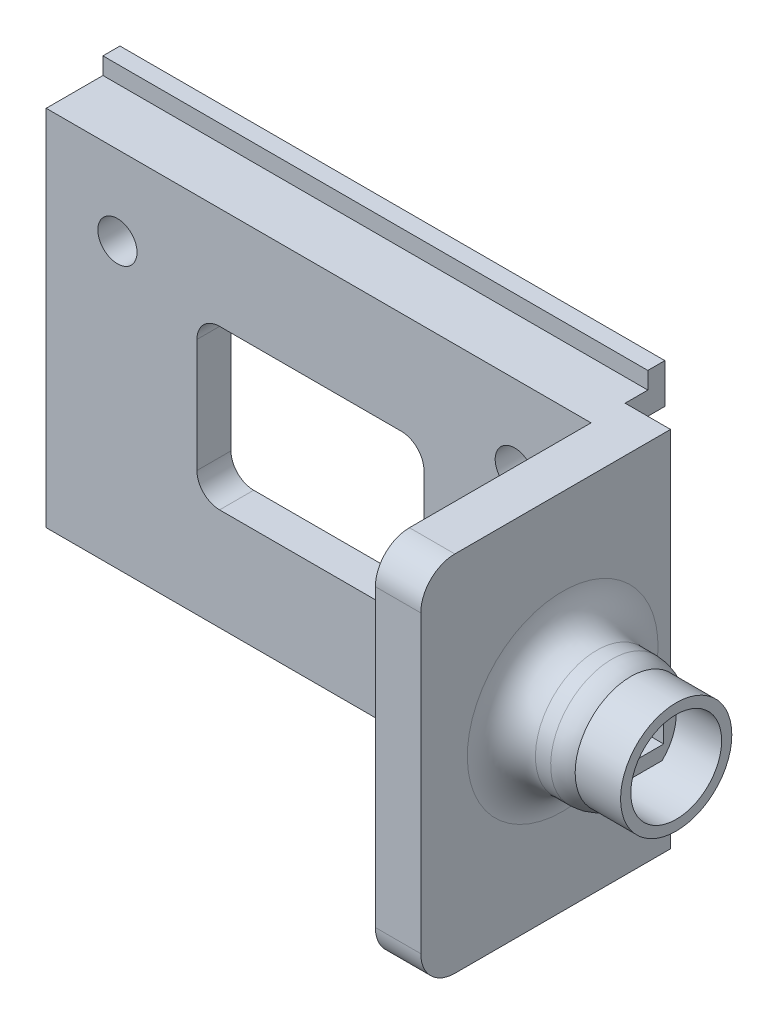
SolidWorks part; units mm, degrees
ref_plane "Front Plane" through (0, 0, 0) normal (0, 0, 1) x (1, 0, 0)
ref_plane "Top Plane" through (0, 0, 0) normal (0, 1, 0) x (1, 0, 0)
ref_plane "Right Plane" through (0, 0, 0) normal (1, 0, 0) x (0, 0, -1)
sketch "Sketch1" plane through (0, 0, 0) normal (0, 0, 1) x (1, 0, 0)
  line L1 (0, 0) -> (52, 0)
  line L2 (0, 0) -> (0, -32)
  line L3 (0, -32) -> (52, -32)
  line L4 (52, 0) -> (52, -32)
  dimension "D1" = 52
  dimension "D2" = 32
extrude "Boss-Extrude1" add sketch "Sketch1" along normal blind 3
ref_plane "Plane1" through (0, 0, 2) normal (0, 0, -1) x (-1, 0, 0)
sketch "Sketch2" plane through (0, 0, 2) normal (0, 0, -1) x (-1, 0, 0)
  line L1 (-48, 0) -> (-52, 0)
  line L2 (-48, 0) -> (-48, -32)
  line L3 (-48, -32) -> (-52, -32)
  line L4 (-52, 0) -> (-52, -32)
  dimension "D1" = 4
extrude "Boss-Extrude2" add sketch "Sketch2" against normal blind 20
fillet "Fillet1" radius 3 2 edges at (50, -32, 22) (50, 0, 22)
sketch "Sketch4" plane through (0, 0, 3) normal (0, 0, 1) x (1, 0, 0)
  line L0 (48, 0) -> (0, 0) construction
  circle A0 centre (41.2777, -7) radius 1.725
  circle A1 centre (6.2777, -7) radius 1.725
  dimension "D1" = 35
  dimension "D2" = 7
  dimension "D3" = 7
extrude "Cut-Extrude2" cut sketch "Sketch4" against normal up to surface (3 mm away) up to face at (26, -16, 0)
sketch "Sketch6" plane through (0, 0, 3) normal (0, 0, 1) x (1, 0, 0)
  line L0 (48, 0) -> (0, 0) construction
  line L1 (33.2777, -9) -> (13.2777, -9)
  line L2 (33.2777, -9) -> (33.2777, -23)
  line L3 (33.2777, -23) -> (13.2777, -23)
  line L4 (13.2777, -9) -> (13.2777, -23)
  circle A0 centre (6.2777, -7) radius 1.725 construction
  dimension "D3" = 7
  dimension "D1" = 14
  dimension "D2" = 20
  dimension "D4" = 9
extrude "Cut-Extrude3" cut sketch "Sketch6" against normal up to surface (3 mm away) up to face at (43.0027, -7, 0)
sketch "Sketch7" plane through (52, 0, 0) normal (1, 0, 0) x (0, 0, -1)
  line L0 (-22, -16) -> (2.0181, -16) construction
  line L1 (-12.4, -17.7) -> (-6.6, -17.7)
  line L2 (-12.4, -17.7) -> (-12.4, -14.3)
  line L3 (-12.4, -14.3) -> (-6.6, -14.3)
  line L4 (-6.6, -17.7) -> (-6.6, -14.3)
  line L5 (-22, -3) -> (-22, -29) construction
  line L6 (-9.5, -32) -> (-9.5, 5.4647) construction
  line L7 (-19, -32) -> (0, -32) construction
  line L8 (-13.6, -13.1) -> (-5.4, -13.1)
  line L9 (-5.4, -18.9) -> (-5.4, -13.1)
  line L10 (-13.6, -18.9) -> (-5.4, -18.9)
  line L11 (-13.6, -18.9) -> (-13.6, -13.1)
  dimension "D5" = 1.2
  dimension "D1" = 5.8
  dimension "D2" = 3.4
  dimension "D3" = 1.7
  dimension "D4" = 2.9
sketch "Sketch8" plane through (52, 0, 0) normal (1, 0, 0) x (0, 0, -1)
  line L0 (-9.5, -16) -> (-9.5, 10.2333) construction
  line L1 (-22, -16) -> (3, -16) construction
  line L3 (0, -32) -> (0, 0) construction
  line L6 (-19, -32) -> (0, -32) construction
  circle A0 centre (-9.5, -16) radius 4.25
  circle A1 centre (-9.5, -16) radius 5.4
  dimension "D1" = 10.8
  dimension "D2" = 8.5
  dimension "D3" = 9.5
  dimension "D4" = 16
extrude "Boss-Extrude4" add sketch "Sketch7" along normal blind 6
sketch "Sketch10" plane through (52, 0, 0) normal (1, 0, 0) x (0, 0, -1)
  line L0 (-19, -32) -> (0, -32) construction
  line L1 (0, -32) -> (0, 0) construction
  circle A0 centre (-9.5, -16) radius 4
  circle A1 centre (-9.5, -16) radius 4.9
  dimension "D1" = 9.8
  dimension "D2" = 8
  dimension "D3" = 16
  dimension "D4" = 9.5
extrude "Boss-Extrude6" add sketch "Sketch10" along normal blind 10
extrude "Boss-Extrude5" add sketch "Sketch8" along normal blind 6
fillet "Fillet2" radius 2 4 edges at (13.2777, -9, 1.5) (13.2777, -23, 1.5) (33.2777, -9, 1.5) (33.2777, -23, 1.5)
fillet "Fillet3" radius 3 2 edges at (52, -21.4, 9.5) (58, -16, 4.1)
sketch "Sketch15" plane through (0, 0, 0) normal (-1, 0, 0) x (0, 0, 1)
  line L1 (3, -32) -> (0, -32) construction
  line L6 (-3.5, -2) -> (-3.5, 1.5)
  line L8 (0, -16) -> (-8.2188, -16) construction
  line L9 (0, 0) -> (0, -32) construction
  line L17 (0, -2) -> (-3.5, -2)
  line L23 (-3.5, -33.5) -> (-2, -33.5)
  line L24 (-3.5, -30) -> (-3.5, -33.5)
  line L25 (0, -30) -> (-3.5, -30)
  line L26 (0, -32) -> (0, -30)
  line L27 (-2, -32) -> (0, -32)
  line L28 (-2, -33.5) -> (-2, -32)
  line L29 (0, 0) -> (0, -2)
  line L30 (-2, 0) -> (0, 0)
  line L31 (-2, 1.5) -> (-2, 0)
  line L32 (-3.5, 1.5) -> (-2, 1.5)
  dimension "D1" = 2
  dimension "D2" = 2
  dimension "D3" = 3.5
extrude "Boss-Extrude7" add sketch "Sketch15" against normal up to surface (48 mm away) up to face at (48, -16, 14.8738)
